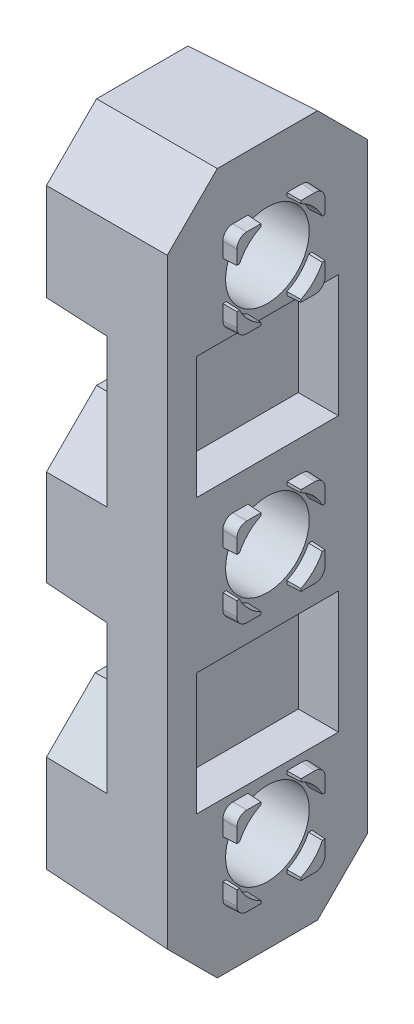
SolidWorks part; units mm, degrees
ref_plane "Front Plane" through (0, 0, 0) normal (0, 0, 1) x (1, 0, 0)
ref_plane "Top Plane" through (0, 0, 0) normal (0, 1, 0) x (1, 0, 0)
ref_plane "Right Plane" through (0, 0, 0) normal (1, 0, 0) x (0, 0, -1)
ref_plane "Plane1" through (88.9762, 0, 0) normal (1, 0, 0) x (0, 0, -1)
sketch "Sketch1" plane through (88.9762, 0, 0) normal (1, 0, 0) x (0, 0, -1)
  line L0 (7.8417, 8.8578) -> (17.5583, 8.8578)
  line L1 (17.5583, 8.8578) -> (17.5583, 43.9743)
  line L2 (17.5583, 43.9743) -> (7.8417, 43.9743)
  line L3 (7.8417, 43.9743) -> (7.8417, 8.8578)
extrude "Boss-Extrude1" add sketch "Sketch1" against normal blind 6.35
sketch "Sketch2" plane through (82.6262, 0, 0) normal (-1, 0, 0) x (0, 0, 1)
  line L0 (-7.8417, 36.5093) -> (-10.3153, 34.0358)
  line L1 (-10.3153, 34.0358) -> (-11.7, 34.0358)
  line L2 (-11.7, 34.0358) -> (-11.7, 31.3853)
  line L3 (-11.7, 31.3853) -> (-10.3802, 31.3853)
  line L4 (-10.3802, 31.3853) -> (-7.8417, 28.8468)
  line L5 (-7.8417, 28.8468) -> (-7.8417, 36.5093)
extrude "Cut-Extrude1" cut sketch "Sketch2" against normal blind 3.175
sketch "Sketch3" plane through (82.6262, 0, 0) normal (-1, 0, 0) x (0, 0, 1)
  line L0 (-7.8417, 23.9852) -> (-10.3802, 21.4468)
  line L1 (-10.3802, 21.4468) -> (-11.7, 21.4468)
  line L2 (-11.7, 21.4468) -> (-11.7, 18.7963)
  line L3 (-11.7, 18.7963) -> (-10.3153, 18.7963)
  line L4 (-10.3153, 18.7963) -> (-7.8417, 16.3228)
  line L5 (-7.8417, 16.3228) -> (-7.8417, 23.9852)
extrude "Cut-Extrude2" cut sketch "Sketch3" against normal blind 3.175
sketch "Sketch4" plane through (82.6262, 0, 0) normal (-1, 0, 0) x (0, 0, 1)
  line L0 (-17.5583, 16.3228) -> (-15.0847, 18.7963)
  line L1 (-15.0847, 18.7963) -> (-13.7, 18.7963)
  line L2 (-13.7, 18.7963) -> (-13.7, 21.4468)
  line L3 (-13.7, 21.4468) -> (-15.0198, 21.4468)
  line L4 (-15.0198, 21.4468) -> (-17.5583, 23.9852)
  line L5 (-17.5583, 23.9852) -> (-17.5583, 16.3228)
extrude "Cut-Extrude3" cut sketch "Sketch4" against normal blind 3.175
sketch "Sketch5" plane through (82.6262, 0, 0) normal (-1, 0, 0) x (0, 0, 1)
  line L0 (-17.5583, 28.8468) -> (-15.0198, 31.3853)
  line L1 (-15.0198, 31.3853) -> (-13.7, 31.3853)
  line L2 (-13.7, 31.3853) -> (-13.7, 34.0358)
  line L3 (-13.7, 34.0358) -> (-15.0847, 34.0358)
  line L4 (-15.0847, 34.0358) -> (-17.5583, 36.5093)
  line L5 (-17.5583, 36.5093) -> (-17.5583, 28.8468)
extrude "Cut-Extrude4" cut sketch "Sketch5" against normal blind 3.175
sketch "Sketch6" plane through (88.9762, 0, 0) normal (1, 0, 0) x (0, 0, -1)
  line L0 (11.7094, 24.3276) -> (11.7094, 24.1554)
  line L1 (11.7094, 24.1554) -> (10.4394, 24.1554)
  line L2 (10.4394, 24.1554) -> (10.4394, 25.4254)
  line L3 (10.4394, 25.4254) -> (10.6116, 25.4254)
  arc A0 (10.6116, 25.4254) -> (11.7094, 24.3276) centre (12.7, 26.416) ccw
extrude "Boss-Extrude2" add sketch "Sketch6" along normal blind 0.6858 draft 2
sketch "Sketch7" plane through (88.9762, 0, 0) normal (1, 0, 0) x (0, 0, -1)
  line L0 (14.7884, 25.4254) -> (14.9606, 25.4254)
  line L1 (14.9606, 25.4254) -> (14.9606, 24.1554)
  line L2 (14.9606, 24.1554) -> (13.6906, 24.1554)
  line L3 (13.6906, 24.1554) -> (13.6906, 24.3276)
  arc A0 (13.6906, 24.3276) -> (14.7884, 25.4254) centre (12.7, 26.416) ccw
extrude "Boss-Extrude3" add sketch "Sketch7" along normal blind 0.6858 draft 2
sketch "Sketch8" plane through (88.9762, 0, 0) normal (1, 0, 0) x (0, 0, -1)
  line L0 (13.6906, 28.5044) -> (13.6906, 28.6766)
  line L1 (13.6906, 28.6766) -> (14.9606, 28.6766)
  line L2 (14.9606, 28.6766) -> (14.9606, 27.4066)
  line L3 (14.9606, 27.4066) -> (14.7884, 27.4066)
  arc A0 (14.7884, 27.4066) -> (13.6906, 28.5044) centre (12.7, 26.416) ccw
extrude "Boss-Extrude4" add sketch "Sketch8" along normal blind 0.6858 draft 2
sketch "Sketch9" plane through (88.9762, 0, 0) normal (1, 0, 0) x (0, 0, -1)
  line L0 (10.6116, 27.4066) -> (10.4394, 27.4066)
  line L1 (10.4394, 27.4066) -> (10.4394, 28.6766)
  line L2 (10.4394, 28.6766) -> (11.7094, 28.6766)
  line L3 (11.7094, 28.6766) -> (11.7094, 28.5044)
  arc A0 (11.7094, 28.5044) -> (10.6116, 27.4066) centre (12.7, 26.416) ccw
extrude "Boss-Extrude5" add sketch "Sketch9" along normal blind 0.6858 draft 2
sketch "Sketch10" plane through (88.9762, 0, 0) normal (1, 0, 0) x (0, 0, -1)
  line L0 (11.7094, 37.0276) -> (11.7094, 36.8554)
  line L1 (11.7094, 36.8554) -> (10.4394, 36.8554)
  line L2 (10.4394, 36.8554) -> (10.4394, 38.1254)
  line L3 (10.4394, 38.1254) -> (10.6116, 38.1254)
  arc A0 (10.6116, 38.1254) -> (11.7094, 37.0276) centre (12.7, 39.116) ccw
extrude "Boss-Extrude6" add sketch "Sketch10" along normal blind 0.6858 draft 2
sketch "Sketch11" plane through (88.9762, 0, 0) normal (1, 0, 0) x (0, 0, -1)
  line L0 (14.7884, 38.1254) -> (14.9606, 38.1254)
  line L1 (14.9606, 38.1254) -> (14.9606, 36.8554)
  line L2 (14.9606, 36.8554) -> (13.6906, 36.8554)
  line L3 (13.6906, 36.8554) -> (13.6906, 37.0276)
  arc A0 (13.6906, 37.0276) -> (14.7884, 38.1254) centre (12.7, 39.116) ccw
extrude "Boss-Extrude7" add sketch "Sketch11" along normal blind 0.6858 draft 2
sketch "Sketch12" plane through (88.9762, 0, 0) normal (1, 0, 0) x (0, 0, -1)
  line L0 (13.6906, 41.2044) -> (13.6906, 41.3766)
  line L1 (13.6906, 41.3766) -> (14.9606, 41.3766)
  line L2 (14.9606, 41.3766) -> (14.9606, 40.1066)
  line L3 (14.9606, 40.1066) -> (14.7884, 40.1066)
  arc A0 (14.7884, 40.1066) -> (13.6906, 41.2044) centre (12.7, 39.116) ccw
extrude "Boss-Extrude8" add sketch "Sketch12" along normal blind 0.6858 draft 2
sketch "Sketch13" plane through (88.9762, 0, 0) normal (1, 0, 0) x (0, 0, -1)
  line L0 (10.6116, 40.1066) -> (10.4394, 40.1066)
  line L1 (10.4394, 40.1066) -> (10.4394, 41.3766)
  line L2 (10.4394, 41.3766) -> (11.7094, 41.3766)
  line L3 (11.7094, 41.3766) -> (11.7094, 41.2044)
  arc A0 (11.7094, 41.2044) -> (10.6116, 40.1066) centre (12.7, 39.116) ccw
extrude "Boss-Extrude9" add sketch "Sketch13" along normal blind 0.6858 draft 2
sketch "Sketch14" plane through (88.9762, 0, 0) normal (1, 0, 0) x (0, 0, -1)
  line L0 (11.7094, 11.6276) -> (11.7094, 11.4554)
  line L1 (11.7094, 11.4554) -> (10.4394, 11.4554)
  line L2 (10.4394, 11.4554) -> (10.4394, 12.7254)
  line L3 (10.4394, 12.7254) -> (10.6116, 12.7254)
  arc A0 (10.6116, 12.7254) -> (11.7094, 11.6276) centre (12.7, 13.716) ccw
extrude "Boss-Extrude10" add sketch "Sketch14" along normal blind 0.6858 draft 2
sketch "Sketch15" plane through (88.9762, 0, 0) normal (1, 0, 0) x (0, 0, -1)
  line L0 (14.7884, 12.7254) -> (14.9606, 12.7254)
  line L1 (14.9606, 12.7254) -> (14.9606, 11.4554)
  line L2 (14.9606, 11.4554) -> (13.6906, 11.4554)
  line L3 (13.6906, 11.4554) -> (13.6906, 11.6276)
  arc A0 (13.6906, 11.6276) -> (14.7884, 12.7254) centre (12.7, 13.716) ccw
extrude "Boss-Extrude11" add sketch "Sketch15" along normal blind 0.6858 draft 2
sketch "Sketch16" plane through (88.9762, 0, 0) normal (1, 0, 0) x (0, 0, -1)
  line L0 (13.6906, 15.8044) -> (13.6906, 15.9766)
  line L1 (13.6906, 15.9766) -> (14.9606, 15.9766)
  line L2 (14.9606, 15.9766) -> (14.9606, 14.7066)
  line L3 (14.9606, 14.7066) -> (14.7884, 14.7066)
  arc A0 (14.7884, 14.7066) -> (13.6906, 15.8044) centre (12.7, 13.716) ccw
extrude "Boss-Extrude12" add sketch "Sketch16" along normal blind 0.6858 draft 2
sketch "Sketch17" plane through (88.9762, 0, 0) normal (1, 0, 0) x (0, 0, -1)
  line L0 (10.6116, 14.7066) -> (10.4394, 14.7066)
  line L1 (10.4394, 14.7066) -> (10.4394, 15.9766)
  line L2 (10.4394, 15.9766) -> (11.7094, 15.9766)
  line L3 (11.7094, 15.9766) -> (11.7094, 15.8044)
  arc A0 (11.7094, 15.8044) -> (10.6116, 14.7066) centre (12.7, 13.716) ccw
extrude "Boss-Extrude13" add sketch "Sketch17" along normal blind 0.6858 draft 2
sketch "Sketch18" plane through (88.9762, 0, 0) normal (1, 0, 0) x (0, 0, -1)
  line L0 (9.1, 16.366) -> (16.3, 16.366)
  line L1 (16.3, 16.366) -> (16.3, 22.566)
  line L2 (16.3, 22.566) -> (9.1, 22.566)
  line L3 (9.1, 22.566) -> (9.1, 16.366)
extrude "Cut-Extrude5" cut sketch "Sketch18" against normal blind 2.032
sketch "Sketch19" plane through (88.9762, 0, 0) normal (1, 0, 0) x (0, 0, -1)
  line L0 (9.1, 36.466) -> (9.1, 30.266)
  line L1 (9.1, 30.266) -> (16.3, 30.266)
  line L2 (16.3, 30.266) -> (16.3, 36.466)
  line L3 (16.3, 36.466) -> (9.1, 36.466)
extrude "Cut-Extrude6" cut sketch "Sketch19" against normal blind 2.032
draft "Draft1" type of draft neutral plane draft angle 2.827 faces to draft 4 face at (84.2137, 30.116, -9.111) face at (84.2137, 22.716, -9.111) face at (84.2137, 22.716, -16.289) face at (84.2137, 30.116, -16.289) neutral plane through (82.6262, 0, 0) neutral plane normal (-1, 0, 0) parameters "D1"=2.827
draft "Draft2" type of draft neutral plane draft angle 2 faces to draft 16 face at (85.8012, 43.9743, -12.7) face at (84.2137, 35.2725, -9.0785) face at (84.2137, 34.0358, -11.0076) face at (84.2137, 31.3853, -10.9847) face at (84.2137, 21.4468, -10.9847) face at (84.2137, 18.7963, -11.0076) face at (84.2137, 17.5595, -9.0785) face at (84.7429, 26.416, -7.8417) face at (85.8012, 8.8578, -12.7) face at (84.2137, 17.5595, -16.3215) face at (84.2137, 18.7963, -14.3924) face at (84.2137, 21.4468, -14.4153) face at (84.2137, 31.3853, -14.4153) face at (84.2137, 34.0358, -14.3924) face at (84.2137, 35.2725, -16.3215) face at (84.7429, 26.416, -17.5583) neutral plane through (82.6262, 0, 0) neutral plane normal (-1, 0, 0) parameters "D1"=2
hole_wizard "#6 Clearance Hole1" positions "Sketch21" profile "Sketch20" hole size "#6" standard "ANSI Inch"
sketch "Sketch21" plane through (82.6262, 0, 0) normal (-1, 0, 0) x (0, 0, 1)
  point P0 (-12.7, 26.416)
  point P1 (-12.7, 13.716)
  point P2 (-12.7, 39.116)
sketch "Sketch20" plane through (82.6262, 26.416, -12.7) normal (0, 1, 0) x (0, 0, 1)
  line L0 (0, 0) -> (0, 7.0358)
  line L1 (0, 7.0358) -> (2.1209, 7.0358)
  line L2 (2.1209, 7.0358) -> (2.1209, 0)
  line L5 (2.1209, 0) -> (0, 0)
  line L11 (0, -6.35) -> (0, 107.95) construction
  dimension "Thru Hole Dia." = 4.2418
  dimension "Thru Hole Depth" = 7.0358
chamfer "Chamfer1" distance 2.5369 angle 44.965 4 edges at (85.8012, 8.7469, -17.6691) (85.8012, 44.0851, -17.6691) (85.8012, 8.7469, -7.7309) (85.8012, 44.0851, -7.7309) first distance on face at (85.8012, 8.7469, -12.7) first distance on face at (85.8012, 44.0851, -12.7)
fillet "Fillet1" radius 0.508 12 edges at (89.3191, 41.3646, -10.4514) (89.3191, 15.9646, -10.4514) (89.3191, 11.4674, -14.9486) (89.3191, 24.1674, -10.4514) (89.3191, 41.3646, -14.9486) (89.3191, 24.1674, -14.9486) (89.3191, 11.4674, -10.4514) (89.3191, 28.6646, -14.9486) (89.3191, 15.9646, -14.9486) (89.3191, 36.8674, -10.4514) (89.3191, 36.8674, -14.9486) (89.3191, 28.6646, -10.4514) tangent propagation no
